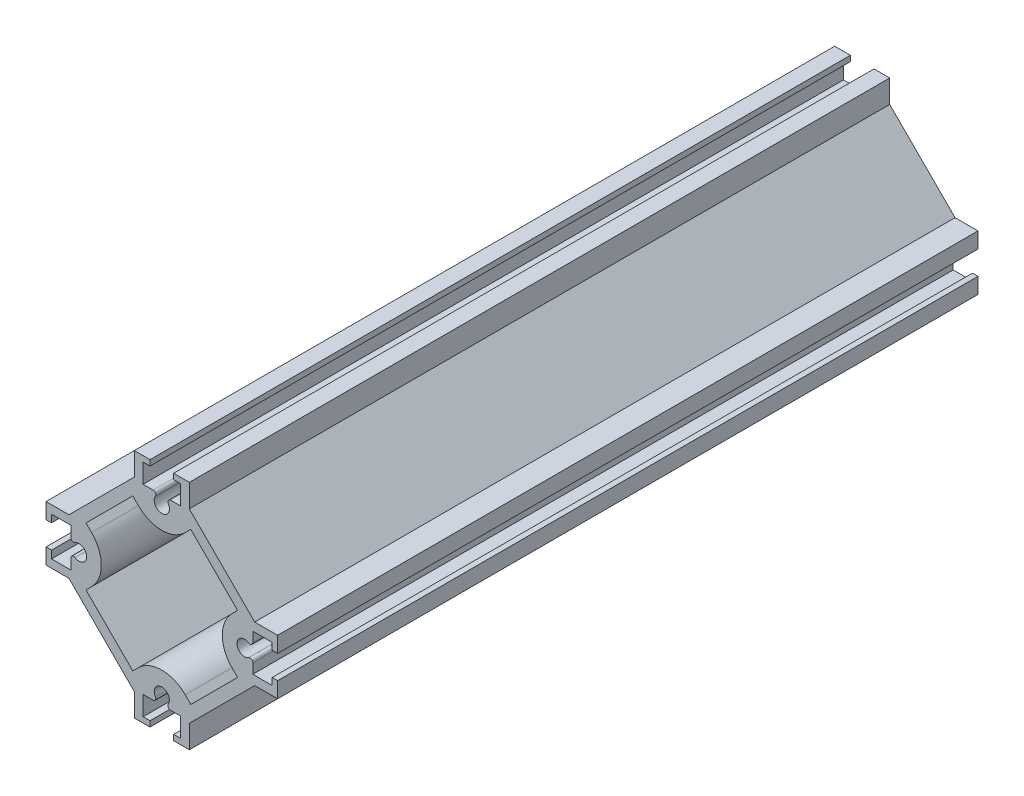
SolidWorks part; units mm, degrees
ref_plane "Front Plane" through (0, 0, 0) normal (0, 0, 1) x (1, 0, 0)
ref_plane "Top Plane" through (0, 0, 0) normal (0, 1, 0) x (1, 0, 0)
ref_plane "Right Plane" through (0, 0, 0) normal (1, 0, 0) x (0, 0, -1)
sketch "Sketch1" plane through (0, 0, 0) normal (0, 0, 1) x (1, 0, 0)
  line L0 (4.9903, 16.843) -> (16.843, 4.9903)
  line L1 (16.843, -4.9903) -> (4.9903, -16.843)
  line L2 (-4.9903, -16.843) -> (-16.843, -4.9903)
  line L3 (-16.843, 4.9903) -> (-4.9903, 16.843)
  line L4 (-16.843, -4.9903) -> (-16.843, 4.9903)
  line L5 (-4.9903, 16.843) -> (4.9903, 16.843)
  line L6 (16.843, 4.9903) -> (16.843, -4.9903)
  line L7 (4.9903, -16.843) -> (-4.9903, -16.843)
  line L12 (0, 8.4853) -> (8.4853, 0) construction
  line L13 (8.4853, 0) -> (0, -8.4853) construction
  line L14 (0, -8.4853) -> (-8.4853, 0) construction
  line L15 (-8.4853, 0) -> (0, 8.4853) construction
  line L16 (0, 8.4853) -> (-5.2598, 13.7451) construction
  line L17 (-8.4853, 0) -> (-13.7451, 5.2598) construction
  line L18 (0, 8.4853) -> (5.2598, 13.7451) construction
  line L19 (-8.4853, 0) -> (-13.7451, -5.2598) construction
  line L20 (0, -8.4853) -> (-5.2598, -13.7451) construction
  line L21 (0, -8.4853) -> (5.2598, -13.7451) construction
  line L22 (8.4853, 0) -> (13.7451, 5.2598) construction
  line L23 (8.4853, 0) -> (13.7451, -5.2598) construction
  line L24 (-13.7451, 5.2598) -> (-5.2598, 13.7451)
  line L25 (5.2598, 13.7451) -> (13.7451, 5.2598)
  line L26 (13.7451, -5.2598) -> (5.2598, -13.7451)
  line L27 (-5.2598, -13.7451) -> (-13.7451, -5.2598)
  circle A0 centre (0, 0) radius 8.4853 construction
  circle A1 centre (0, 0) radius 11 construction
  arc A2 (13.7451, -5.2598) -> (13.7451, 5.2598) centre (19.0048, 0) cw
  arc A3 (5.2598, 13.7451) -> (-5.2598, 13.7451) centre (0, 19.0048) cw
  arc A4 (-13.7451, 5.2598) -> (-13.7451, -5.2598) centre (-19.0048, 0) cw
  arc A5 (-5.2598, -13.7451) -> (5.2598, -13.7451) centre (0, -19.0048) cw
  arc A10 (4.9903, 16.843) -> (-4.9903, 16.843) centre (0, 19.0048) cw construction
  arc A11 (-16.843, 4.9903) -> (-16.843, -4.9903) centre (-19.0048, 0) cw construction
  arc A12 (16.843, -4.9903) -> (16.843, 4.9903) centre (19.0048, 0) cw construction
  arc A13 (-4.9903, -16.843) -> (4.9903, -16.843) centre (0, -19.0048) cw construction
  dimension "D1" = 12
  dimension "D3" = 2
  dimension "D2" = 22
extrude "Boss-Extrude1" add sketch "Sketch1" along normal blind 127
sketch "Sketch2" plane through (0, 0, 0) normal (0, 0, 1) x (1, 0, 0)
  line L0 (21, -21) -> (-21, -21) construction
  line L1 (0, 0) -> (0, -21) construction
  line L2 (21, -21) -> (21, 21) construction
  line L3 (-21, -21) -> (-21, 21) construction
  line L5 (0, 0) -> (-21, 0) construction
  line L7 (-21, 21) -> (21, 21) construction
  circle A0 centre (0, 0) radius 11 construction
  circle A1 centre (-15.0048, 0) radius 1.375
  circle A4 centre (0, 15.0048) radius 1.375
  circle A5 centre (15.0048, 0) radius 1.375
  circle A6 centre (0, -15.0048) radius 1.375
  arc A13 (-5.2598, 13.7451) -> (5.2598, 13.7451) centre (0, 19.0048) ccw construction
  arc A14 (13.7451, 5.2598) -> (13.7451, -5.2598) centre (19.0048, 0) ccw construction
  arc A15 (5.2598, -13.7451) -> (-5.2598, -13.7451) centre (0, -19.0048) ccw construction
  arc A16 (-13.7451, -5.2598) -> (-13.7451, 5.2598) centre (-19.0048, 0) ccw construction
  point P3 (0, -21)
  point P12 (-21, 0)
  dimension "D2" = 42
  dimension "D3" = 22
  dimension "D4" = 4
  dimension "D5" = 2.75
  dimension "D6" = 4
  dimension "D7" = 4
  dimension "D8" = 4
  dimension "D1" = 42
sketch "Sketch5" plane through (0, 0, 127) normal (0, 0, 1) x (1, 0, 0)
  line L0 (-16.843, -4.9903) -> (-21, -4.9903)
  line L2 (-16.843, 4.9903) -> (-21, 4.9903)
  line L3 (16.843, 4.9903) -> (21, 4.9903)
  line L4 (21, -21) -> (21, 21) construction
  line L6 (21, -4.9903) -> (16.843, -4.9903)
  line L7 (-21, 4.9903) -> (-21, 2.1403)
  line L9 (-21, 2.1403) -> (-20, 2.1403)
  line L10 (-20, 3.5143) -> (-16.843, 3.5143)
  line L13 (-20, 2.1403) -> (-20, 3.5143)
  line L14 (-20, -3.5137) -> (-16.843, -3.5137)
  line L15 (-16.843, 4.9903) -> (-16.843, 3.5143)
  line L16 (-16.843, -3.5137) -> (-16.843, -4.9903)
  line L17 (21, 4.9903) -> (21, 2.1403)
  line L18 (21, 2.1403) -> (20, 2.1403)
  line L19 (20, 2.1403) -> (20, 3.3903)
  line L20 (20, 3.3903) -> (16.843, 3.3903)
  line L21 (16.843, -4.9903) -> (16.843, -3.3903)
  line L22 (21, -4.9903) -> (21, -2.1403)
  line L23 (21, -2.1403) -> (20, -2.1403)
  line L24 (20, -2.1403) -> (20, -3.3903)
  line L25 (20, -3.3903) -> (16.843, -3.3903)
  line L26 (16.843, 4.9903) -> (16.843, 3.3903)
  line L27 (3.3903, 16.843) -> (4.9903, 16.843)
  line L28 (-4.9903, 16.843) -> (-4.9903, 21)
  line L29 (-21, 21) -> (21, 21) construction
  line L30 (-4.9903, 21) -> (-2.1403, 21)
  line L31 (-2.1403, 21) -> (-2.1403, 20)
  line L32 (-2.1403, 20) -> (-3.3903, 20)
  line L33 (-3.3903, 20) -> (-3.3903, 16.843)
  line L34 (-4.9903, 16.843) -> (-3.3903, 16.843)
  line L35 (4.9903, 16.843) -> (4.9903, 21)
  line L36 (4.9903, 21) -> (2.1403, 21)
  line L37 (2.1403, 21) -> (2.1403, 20)
  line L38 (2.1403, 20) -> (3.3903, 20)
  line L39 (3.3903, 20) -> (3.3903, 16.843)
  line L40 (4.9903, -16.843) -> (4.9903, -21)
  line L42 (4.9903, -21) -> (2.1403, -21)
  line L43 (2.1403, -21) -> (2.1403, -20)
  line L44 (2.1403, -20) -> (3.3903, -20)
  line L45 (3.3903, -20) -> (3.3903, -16.843)
  line L46 (21, -21) -> (-21, -21) construction
  line L47 (-4.9903, -16.843) -> (-4.9903, -21)
  line L48 (-4.9903, -21) -> (-2.1403, -21)
  line L49 (-2.1403, -21) -> (-2.1403, -20)
  line L50 (-2.1403, -20) -> (-3.3903, -20)
  line L51 (-3.3903, -20) -> (-3.3903, -16.843)
  line L52 (-4.9903, -16.843) -> (-3.3903, -16.843)
  line L53 (3.3903, -16.843) -> (4.9903, -16.843)
  line L54 (-21, -21) -> (-21, 21) construction
  line L56 (-20, -3.5137) -> (-20, -2.1403)
  line L57 (-20, -2.1403) -> (-21, -2.1403)
  line L58 (-21, -2.1403) -> (-21, -4.9903)
  dimension "D3" = 1
  dimension "D6" = 1
  dimension "D7" = 1
  dimension "D8" = 2.85
  dimension "D9" = 1.6
  dimension "D10" = 1
  dimension "D11" = 2.85
  dimension "D12" = 1.6
  dimension "D13" = 1
  dimension "D14" = 2.85
  dimension "D15" = 1.6
  dimension "D16" = 1
  dimension "D17" = 2.85
  dimension "D18" = 1.6
  dimension "D19" = 1.6
  dimension "D20" = 1
  dimension "D21" = 2.85
  dimension "D22" = 1
  dimension "D23" = 2.85
  dimension "D24" = 1.6
  dimension "D25" = 2.85
  dimension "D26" = 2.85
  dimension "D27" = 4.2806
  dimension "D30" = 4.157
  dimension "D31" = 4.157
  dimension "D32" = 4.157
  dimension "D33" = 4.157
extrude "Boss-Extrude4" add sketch "Sketch5" against normal through all
sketch "Sketch7" plane through (0, 0, 0) normal (0, 0, 1) x (1, 0, 0)
  line L0 (-16.843, -3.5137) -> (-20, -3.5137) construction
  line L1 (-20, 3.5143) -> (-16.5, 3.5143)
  line L2 (-20, 3.5143) -> (-20, -3.5137)
  line L3 (-20, -3.5137) -> (-16.5, -3.5137)
  line L4 (-16.5, 3.5143) -> (-16.5, -3.5137)
  line L5 (-3.3903, 20) -> (3.3903, 20)
  line L6 (-3.3903, 20) -> (-3.3903, 16.5)
  line L7 (-3.3903, 16.5) -> (3.3903, 16.5)
  line L8 (3.3903, 20) -> (3.3903, 16.5)
  line L9 (20, 3.3903) -> (16.5, 3.3903)
  line L10 (20, 3.3903) -> (20, -3.3903)
  line L11 (20, -3.3903) -> (16.5, -3.3903)
  line L12 (16.5, 3.3903) -> (16.5, -3.3903)
  line L13 (-3.3903, -20) -> (3.3903, -20)
  line L14 (-3.3903, -20) -> (-3.3903, -16.5)
  line L15 (-3.3903, -16.5) -> (3.3903, -16.5)
  line L16 (3.3903, -20) -> (3.3903, -16.5)
  circle A0 centre (-15.0048, 0) radius 1.375
  circle A1 centre (0, 15.0048) radius 1.375
  circle A2 centre (15.0048, 0) radius 1.375
  circle A3 centre (0, -15.0048) radius 1.375
  dimension "D1" = 3.5
  dimension "D2" = 3.5
  dimension "D3" = 3.5
  dimension "D4" = 3.5
extrude "Cut-Extrude2" cut sketch "Sketch7" along normal through all
sketch "Sketch8" plane through (0, 0, 127) normal (0, 0, 1) x (1, 0, 0)
  line L0 (-15.0048, -0.5) -> (-15.0048, 0.5)
  line L2 (-15.0048, 0.5) -> (-17.8395, 0.5)
  line L3 (-17.8395, 0.5) -> (-17.8395, -0.5)
  line L4 (-17.8395, -0.5) -> (-15.0048, -0.5)
  line L5 (0.5, 15.0048) -> (-0.5, 15.0048)
  line L6 (-0.5, 15.0048) -> (-0.5, 17.7531)
  line L7 (-0.5, 17.7531) -> (0.5, 17.7531)
  line L8 (0.5, 17.7531) -> (0.5, 15.0048)
  line L9 (15.0048, -0.5) -> (15.0048, 0.5)
  line L10 (15.0048, 0.5) -> (18.1877, 0.5)
  line L11 (18.1877, 0.5) -> (18.1877, -0.5)
  line L12 (18.1877, -0.5) -> (15.0048, -0.5)
  line L13 (0.5, -15.0048) -> (-0.5, -15.0048)
  line L15 (-0.5, -15.0048) -> (-0.5, -17.5653)
  line L16 (-0.5, -17.5653) -> (0.5, -17.5653)
  line L17 (0.5, -17.5653) -> (0.5, -15.0048)
  point P4 (-15.0048, 0)
  point P11 (0, 15.0048)
  point P18 (15.0048, 0)
  point P25 (0, -15.0048)
  dimension "D1" = 1
  dimension "D2" = 1
extrude "Cut-Extrude3" cut sketch "Sketch8" against normal through all
fillet "Fillet3" radius 0.5 8 edges at (-16.5, 0.5, 63.5) (0.5, -16.5, 63.5) (-0.5, -16.5, 63.5) (16.5, -0.5, 63.5) (16.5, 0.5, 63.5) (-0.5, 16.5, 63.5) (0.5, 16.5, 63.5) (-16.5, -0.5, 63.5)
fillet "Fillet4" radius 0.5 8 edges at (-16.2857, 0.5, 63.5) (0.5, -16.2857, 63.5) (-0.5, -16.2857, 63.5) (16.2857, -0.5, 63.5) (16.2857, 0.5, 63.5) (-0.5, 16.2857, 63.5) (0.5, 16.2857, 63.5) (-16.2857, -0.5, 63.5)
sketch "Sketch9" plane through (0, 0, 127) normal (0, 0, 1) x (1, 0, 0)
  line L0 (-5.2598, 13.7451) -> (-13.7451, 5.2598) construction
  line L1 (13.7451, 5.2598) -> (5.2598, 13.7451) construction
  line L2 (5.2598, -13.7451) -> (13.7451, -5.2598) construction
  line L3 (-13.7451, -5.2598) -> (-5.2598, -13.7451) construction
  line L4 (-5.2598, 13.7451) -> (-13.7451, 5.2598)
  line L5 (13.7451, 5.2598) -> (5.2598, 13.7451)
  line L6 (5.2598, -13.7451) -> (13.7451, -5.2598)
  line L7 (-13.7451, -5.2598) -> (-5.2598, -13.7451)
  line L8 (-5.2598, 13.7451) -> (0, 8.4853)
  line L9 (0, 8.4853) -> (5.2598, 13.7451)
  line L10 (13.7451, 5.2598) -> (8.4853, 0)
  line L11 (8.4853, 0) -> (13.7451, -5.2598)
  line L12 (5.2598, -13.7451) -> (0, -8.4853)
  line L13 (0, 0) -> (0, -21) construction
  line L14 (0, -8.4853) -> (-5.2598, -13.7451)
  line L15 (-13.7451, -5.2598) -> (-8.4853, 0)
  line L16 (0, 0) -> (-21, 0) construction
  line L17 (-8.4853, 0) -> (-13.7451, 5.2598)
  line L18 (-4.9903, 16.843) -> (-16.843, 4.9903) construction
  line L19 (16.843, 4.9903) -> (4.9903, 16.843) construction
  line L20 (4.9903, -16.843) -> (16.843, -4.9903) construction
  line L21 (-16.843, -4.9903) -> (-4.9903, -16.843) construction
  line L22 (-4.9903, 16.843) -> (-16.843, 4.9903)
  line L23 (16.843, 4.9903) -> (4.9903, 16.843)
  line L24 (4.9903, -16.843) -> (16.843, -4.9903)
  line L25 (-16.843, -4.9903) -> (-4.9903, -16.843)
  arc A4 (-16.843, 4.9903) -> (-16.843, -4.9903) centre (-16.843, 0) cw
  arc A5 (-4.9903, 16.843) -> (4.9903, 16.843) centre (0, 16.843) ccw
  arc A6 (16.843, 4.9903) -> (16.843, -4.9903) centre (16.843, 0) ccw
  arc A7 (4.9903, -16.843) -> (-4.9903, -16.843) centre (0, -16.843) ccw
extrude "Boss-Extrude6" add sketch "Sketch9" against normal through all
fillet "Fillet5" radius 6 4 edges at (8.4853, 0, 63.5) (0, -8.4853, 63.5) (-8.4853, 0, 63.5) (0, 8.4853, 63.5)
sketch "Sketch13" plane through (0, 0, 127) normal (0, 0, 1) x (1, 0, 0)
  line L0 (-5.2598, 13.7451) -> (-13.7451, 5.2598) construction
  line L1 (-9.5024, 9.5024) -> (9.5024, -9.5024) construction
  line L2 (5.2598, -13.7451) -> (13.7451, -5.2598) construction
  dimension "D1" = 12
  dimension "D2" = 26.8769
